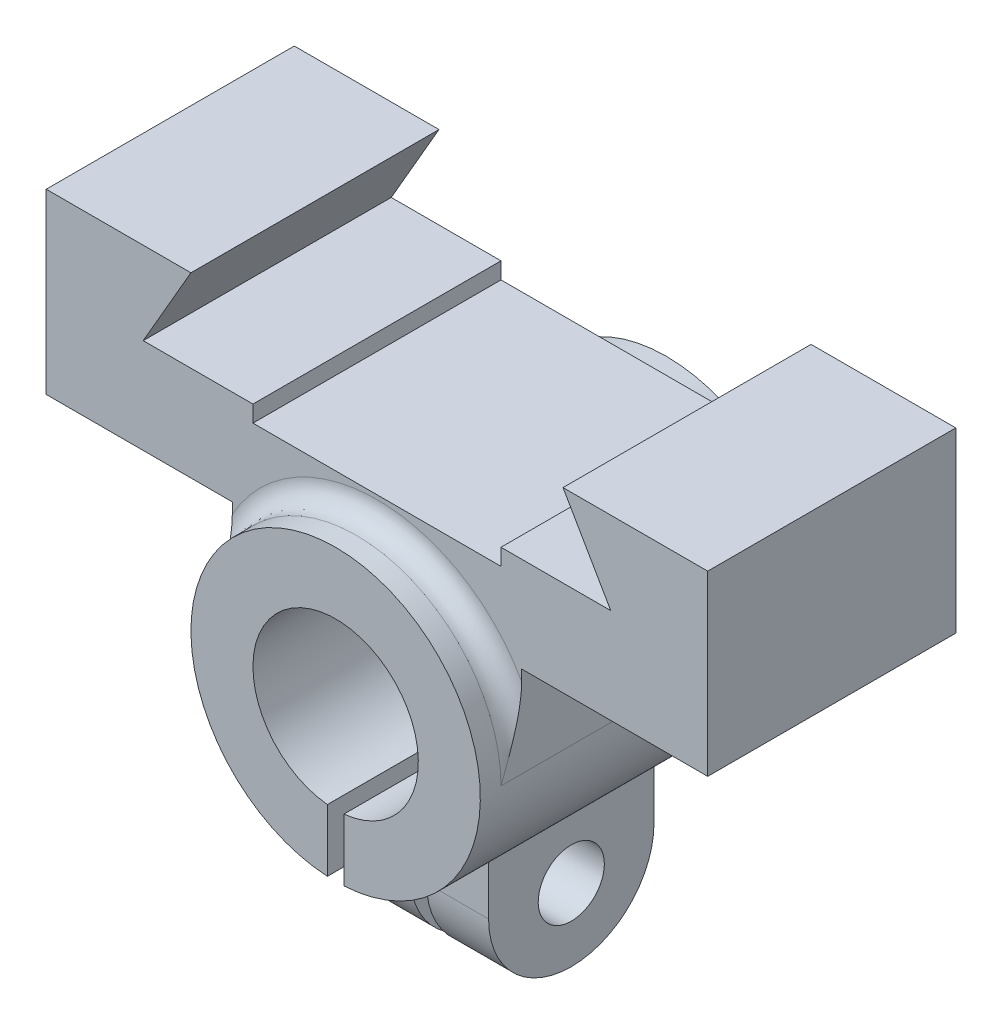
SolidWorks part; units mm, degrees
ref_plane "Front Plane" through (0, 0, 0) normal (0, 0, 1) x (1, 0, 0)
ref_plane "Top Plane" through (0, 0, 0) normal (0, 1, 0) x (1, 0, 0)
ref_plane "Right Plane" through (0, 0, 0) normal (1, 0, 0) x (0, 0, -1)
sketch "Sketch1" plane through (0, 0, 0) normal (0, 0, 1) x (1, 0, 0)
  line L0 (-84.3061, -1.1693) -> (-84.3061, 20.8307)
  line L1 (-84.3061, 20.8307) -> (-39.3061, 20.8307)
  line L2 (-39.3061, 20.8307) -> (-39.3061, 63.8307)
  line L3 (-39.3061, 63.8307) -> (-74.3061, 63.8307)
  line L4 (-74.3061, 63.8307) -> (-62.7591, 43.8307)
  line L5 (-62.7591, 43.8307) -> (-89.3061, 43.8307)
  line L6 (-89.3061, 43.8307) -> (-89.3061, 39.8307)
  line L7 (-89.3061, 39.8307) -> (-119.3061, 39.8307)
  line L8 (-119.3061, 72.0529) -> (-119.3061, -60.7883) construction
  line L10 (-119.3061, 18.8307) -> (-119.3061, 33.8307)
  line L11 (-119.3061, -65.5465) -> (-102.3061, -65.5465)
  line L12 (-102.3061, -65.5465) -> (-102.3061, -31.7634)
  line L13 (-119.3061, 39.8307) -> (-119.3061, 33.8307)
  line L14 (-119.3061, -65.5465) -> (-119.3061, -36.1693)
  line L15 (-93.0793, -69.1693) -> (-93.0793, -49.1693) construction
  line L16 (-88.3061, -49.1693) -> (-129.81, -49.1693) construction
  line L17 (-110.8061, -65.5465) -> (-110.8061, -39.3393) construction
  line L18 (-117.3061, -65.5465) -> (-117.3061, -36.1121)
  line L19 (-117.3061, -36.1121) -> (-117.3061, -21.0691)
  line L20 (-129.81, -1.1693) -> (-104.6323, -1.1693) construction
  arc A4 (-119.3061, 33.8307) -> (-117.3061, -36.1121) centre (-119.3061, -1.1693) cw
  arc A5 (-119.3061, 18.8307) -> (-117.3061, -21.0691) centre (-119.3061, -1.1693) cw
  point P25 (-110.8061, -49.1693)
  dimension "D3" = 65
  dimension "D4" = 60
  dimension "D5" = 4
  dimension "D6" = 45
  dimension "D7" = 80
  dimension "D8" = 20
  dimension "D9" = 30
  dimension "D10" = 17
  dimension "D11" = 43
  dimension "D12" = 2
extrude "Boss-Extrude4" add sketch "Sketch1" along normal blind 40 and the other way blind 40 contours L10 region at (-89.8139, -18.5209, 0)
extrude "Boss-Extrude5" add sketch "Sketch1<10>" along normal blind 30 and the other way blind 30 contours L13 L0 L1 L2 L3 L4 L5 L6 L7 region at (-67.6625, 38.2132, 0)
sketch "Sketch1<10>" plane through (0, 0, 0) normal (0, 0, 1) x (1, 0, 0) same geometry as "Sketch1"
extrude "Boss-Extrude6" add sketch "Sketch1<11>" along normal blind 20 and the other way blind 20 contours L12 L14 L11 region at (-109.6326, -50.0231, 0)
sketch "Sketch1<11>" plane through (0, 0, 0) normal (0, 0, 1) x (1, 0, 0) same geometry as "Sketch1"
fillet "Fillet6" radius 20 2 edges at (-109.8061, -65.5465, 20) (-109.8061, -65.5465, -20)
sketch "Sketch7" plane through (-102.3061, 0, 0) normal (1, 0, 0) x (0, 0, -1)
  line L2 (0, 0) -> (0, -48) construction
  circle A2 centre (0, -48) radius 8
extrude "Cut-Extrude2" cut sketch "Sketch7" against normal blind 20
fillet "Fillet9" radius 5 2 edges at (-94.5573, 23.5794, -30) (-94.5573, 23.5794, 30)
mirror "Mirror1" about plane through (-119.3061, 0, -40) normal (1, 0, 0) of bodies 108
